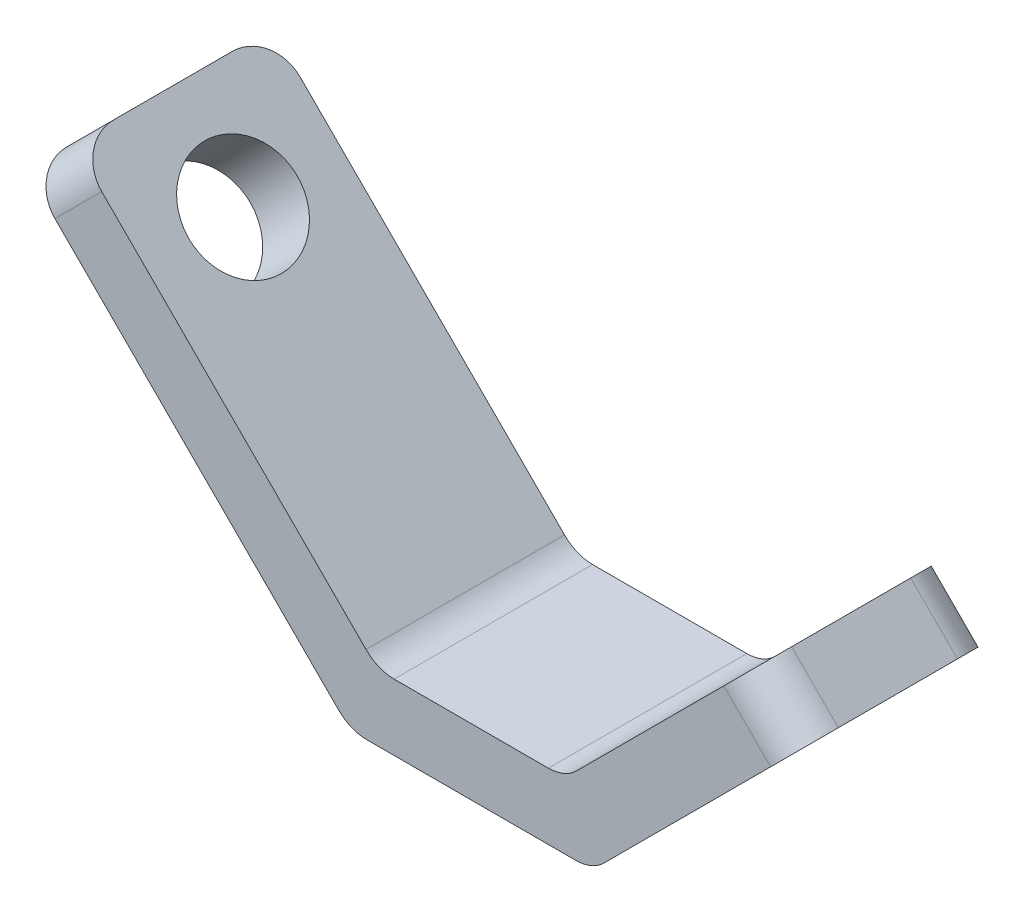
SolidWorks part; units mm, degrees
ref_plane "正面" through (0, 0, 0) normal (0, 0, 1) x (1, 0, 0)
ref_plane "平面" through (0, 0, 0) normal (0, 1, 0) x (1, 0, 0)
ref_plane "右側面" through (0, 0, 0) normal (1, 0, 0) x (0, 0, -1)
sketch "ｽｹｯﾁ1" plane through (0, 0, 0) normal (0, 0, 1) x (1, 0, 0)
  line L0 (0, 0) -> (-24.4454, 24.4454)
  line L1 (-24.4454, 24.4454) -> (-20.9099, 27.981)
  line L2 (-20.9099, 27.981) -> (2.0711, 5)
  line L3 (2.0711, 5) -> (16.2132, 5)
  line L4 (16.2132, 5) -> (30.3553, 19.1421)
  line L5 (30.3553, 19.1421) -> (33.8909, 15.6066)
  line L6 (33.8909, 15.6066) -> (18.2843, 0)
  line L7 (18.2843, 0) -> (0, 0)
  point P6 (23.2843, 12.0711)
  point P10 (-15.6066, 22.6777)
  dimension "D1" = 135
  dimension "D2" = 135
  dimension "D3" = 5
  dimension "D4" = 5
  dimension "D5" = 5
  dimension "D8" = 25
  dimension "D6" = 7.5
  dimension "D7" = 40
  dimension "D9" = 20
extrude "ﾎﾞｽ - 押し出し1" add sketch "ｽｹｯﾁ1" along normal mid plane 15
sketch "ｽｹｯﾁ2" plane through (0, 0, 0) normal (-0.7071, -0.7071, 0) x (0, 0, 1)
  line L1 (7.5, 34.5711) -> (-7.5, 34.5711) construction
  circle A0 centre (0, 27.0711) radius 4.1
  dimension "D1" = 8.2
  dimension "D2" = 7.5
extrude "ｶｯﾄ - 押し出し1" cut sketch "ｽｹｯﾁ2" against normal through all both and the other way through all
sketch "ｽｹｯﾁ3" plane through (9.1421, -9.1421, 0) normal (0.7071, -0.7071, 0) x (0, 0, -1)
  line L0 (-7.5, 35) -> (-7.5, 15) construction
  line L1 (-7.5, 35) -> (7.5, 35) construction
  circle A0 centre (0, 27.5) radius 4.1
  point P4 (-7.5, 25)
  point P7 (0, 35)
  point P8 (0, 0)
  dimension "D1" = 8.2
  dimension "D2" = 7.5
extrude "ｶｯﾄ - 押し出し2" cut sketch "ｽｹｯﾁ3" against normal through all both and the other way through all
fillet "ﾌｨﾚｯﾄ1" radius 3 8 edges at (32.1231, 17.3744, -7.5) (32.1231, 17.3744, 7.5) (-22.6777, 26.2132, -7.5) (-22.6777, 26.2132, 7.5) (18.2843, 0, 0) (0, 0, 0) (16.2132, 5, 0) (2.0711, 5, 0)
equation "\"D4@ｽｹｯﾁ1\"=\"D3@ｽｹｯﾁ1\""
equation "\"D5@ｽｹｯﾁ1\"=\"D3@ｽｹｯﾁ1\""
